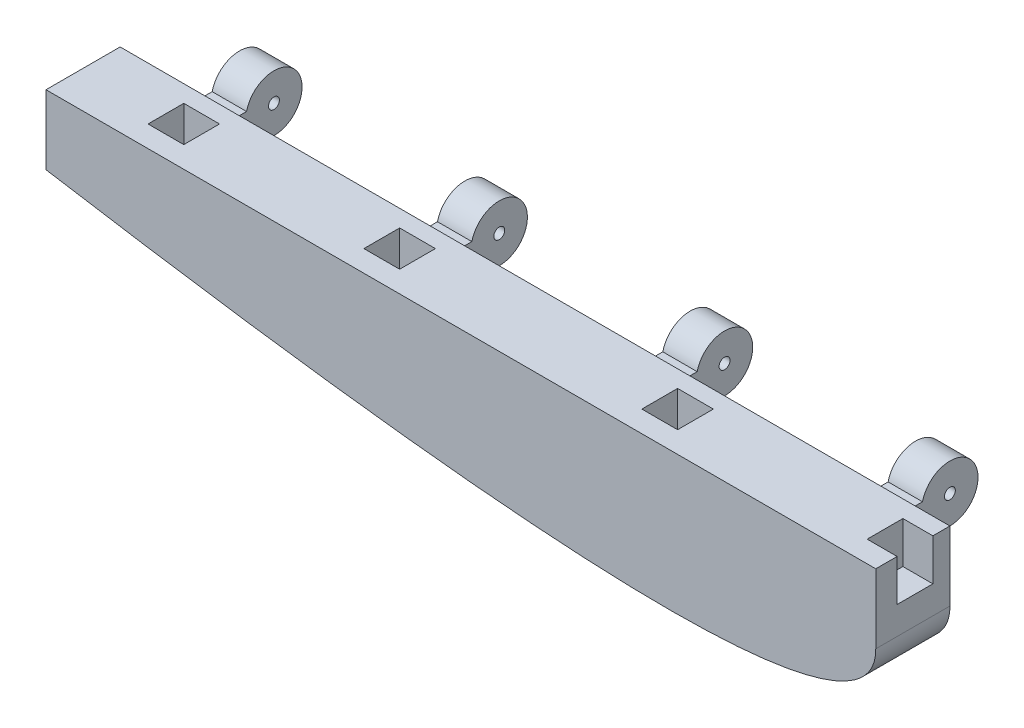
SolidWorks part; units mm, degrees
material "ABS"
ref_plane "Front Plane" through (0, 0, 0) normal (0, 0, 1) x (1, 0, 0)
ref_plane "Top Plane" through (0, 0, 0) normal (0, 1, 0) x (1, 0, 0)
ref_plane "Right Plane" through (0, 0, 0) normal (1, 0, 0) x (0, 0, -1)
sketch "Sketch2" plane through (0, 0, 0) normal (0, 1, 0) x (1, 0, 0)
  line L0 (0, 0) -> (-152, 0)
  line L1 (-152, 0) -> (-152, -152.4)
  line L2 (-152, -152.4) -> (0, -152.4)
  line L3 (0, -152.4) -> (0, 0)
  dimension "D1" = 152.4
  dimension "D2" = 152
extrude "Boss-Extrude2" add sketch "Sketch2" along normal blind 12.7
ref_plane "Plane2" through (-14.9327, 0, 0) normal (1, 0, 0) x (0, 0, -1)
ref_plane "Plane1" through (-12.7, 0, 0) normal (1, 0, 0) x (0, 0, -1)
sketch "Sketch9" plane through (0, 12.7, 0) normal (0, 1, 0) x (1, 0, 0)
  line L0 (0, 0) -> (0, -48.862) construction
  line L1 (0, -152.4) -> (0, 0) construction
  line L2 (-152, 0) -> (-152, -48.862) construction
  line L3 (-152, 0) -> (-152, -152.4) construction
  line L4 (0, 0) -> (-5.4077, 0) construction
  line L5 (0, 0) -> (-152, 0) construction
  dimension "D1" = 48.862
  dimension "D2" = 48.862
  dimension "D3" = 5.4077
ref_axis "Axis2" through (-152, 12.7, 48.862) along (1, 0, 0)
sketch "Sketch3" plane through (-12.7, 0, 0) normal (1, 0, 0) x (0, 0, -1)
  line L0 (0, 6.35) -> (0, 0)
  line L2 (0, 12.7) -> (0, 0) construction
  line L3 (0, 0) -> (12.7, 0)
  line L4 (12.7, 6.1562) -> (12.7, 6.1587)
  line L5 (7.6839, 6.35) -> (0, 6.35)
  arc A3 (12.7, 0) -> (7.6839, 6.35) centre (12.7, 5.1562) ccw
  circle A5 centre (12.7, 5.1562) radius 1
  dimension "D3" = 10.3124
  dimension "D2" = 0
  dimension "D4" = 7.6839
  dimension "D6" = 2
  dimension "D1" = 6.35
  dimension "D5" = 12.7
extrude "Boss-Extrude3" add sketch "Sketch3" against normal blind 6.3 contours A5 L4 L3 A3 | A5 L4 A3 L3 | A3 L5 L0 L3 region at (-12.7, 4.2781, -9.3369)
ref_plane "Plane5" through (0, 0, 24.431) normal (0, 0, -1) x (-1, 0, 0)
ref_plane "Plane6" through (0, 12.7, 0) normal (0, 1, 0) x (1, 0, 0)
sketch "Sketch10" plane through (0, 12.7, 0) normal (0, 1, 0) x (1, 0, 0)
  line L0 (0, 0) -> (-152, 0) construction
  circle A0 centre (-10.2337, -3.175) radius 0.508
  dimension "D1" = 10.2337
  dimension "D3" = 1.016
  dimension "D2" = 3.175
extrude "Cut-Extrude3" [suppressed] cut sketch "Sketch10" against normal blind 9.525
mirror "Mirror1" [suppressed] about plane through (0, 0, 24.431) normal (0, 0, -1)
fillet "Fillet1" radius 1.5875 3 edges at (-19, 3.175, 0) (-15.85, 6.35, 0) (-12.7, 3.175, 0)
pattern_linear "LPattern1" count 4 spacing 41.275 along (-1, 0, 0) of "Boss-Extrude3", "Mirror1", "Fillet1"
sketch "Sketch12" plane through (0, 0, 0) normal (0, 0, -1) x (-1, 0, 0)
  spline S0 degree 1 poles (0, 0) (152, 0) knots 0 0 1 1
  spline S1 degree 2 poles (152, 0) (-0.2287, -25.399) (0, 0) knots 0 0 0 0.553499 0.553499 0.553499
  spline S2 degree 1 poles (0, 0) (152, 0) knots 0 0 1 1
  spline S3 degree 1 poles (152, 0) (0, 0) knots 0 0 1 1
  dimension "D1" = 50.8
extrude "Boss-Extrude4" add sketch "Sketch12" against normal up to surface (152.4 mm away) contours S1 | S0 S1 up to face at (-76, 6.35, 152.4)
sketch "Sketch13" plane through (0, 12.7, 0) normal (0, 1, 0) x (1, 0, 0)
  line L0 (0, -152.4) -> (0, 0) construction
  line L1 (-81.8426, -69.85) -> (-19.05, -69.85)
  line L2 (-81.8426, -69.85) -> (-81.8426, -96.44)
  line L3 (-81.8426, -96.44) -> (-19.05, -96.44)
  line L4 (-19.05, -69.85) -> (-19.05, -96.44)
  line L5 (0, 0) -> (-152, 0) construction
  line L7 (-85.0176, -66.675) -> (-15.875, -66.675)
  line L8 (-85.0176, -66.675) -> (-85.0176, -99.615)
  line L9 (-85.0176, -99.615) -> (-15.875, -99.615)
  line L10 (-15.875, -66.675) -> (-15.875, -99.615)
  dimension "D1" = 62.7926
  dimension "D2" = 26.59
  dimension "D3" = 19.05
  dimension "D4" = 69.85
  dimension "D5" = 3.175
  dimension "D6" = 3.175
  dimension "D7" = 3.175
  dimension "D8" = 3.175
extrude "Boss-Extrude5" add sketch "Sketch13" along normal blind 3.5001
sketch "Sketch14" plane through (0, 12.7, 0) normal (0, 1, 0) x (1, 0, 0)
  line L0 (-19.05, -69.85) -> (-81.8426, -69.85) construction
  line L1 (-81.8426, -69.85) -> (-81.8426, -96.44) construction
  circle A0 centre (-78.1761, -74.1223) radius 1.2497
  circle A1 centre (-22.1767, -74.1223) radius 1.2497
  circle A2 centre (-78.1761, -93.1215) radius 1.2497
  circle A3 centre (-22.1767, -93.1215) radius 1.2497
  dimension "D1" = 4.2723
  dimension "D3" = 3.6665
  dimension "D4" = 55.9994
  dimension "D2" = 18.9992
extrude "Cut-Extrude5" cut sketch "Sketch14" against normal blind 6.35
sketch "Sketch15" plane through (0, 12.7, 0) normal (0, 1, 0) x (1, 0, 0)
  line L0 (-101.2, -152.4) -> (-101.2, -127)
  line L1 (-152, -152.4) -> (0, -152.4) construction
  line L2 (-101.2, -127) -> (-152, -66.4589)
  line L3 (-152, 0) -> (-152, -152.4) construction
  line L4 (-152, -66.4589) -> (-152, -152.4)
  line L5 (-152, -152.4) -> (-101.2, -152.4)
  spline S0 degree 3 poles (-101.2, -127) (-102.2273, -119.2728) (-124.4228, -68.0569) (-152, -66.4589) knots 0 0 0 0 0.841715 0.841715 0.841715 0.841715
  line M9 (-152, 0) -> (-152, -152.4)
  line M10 (-152, -152.4) -> (0, -152.4)
  dimension "D1" = 50.8
  dimension "D2" = 25.4
  dimension "D3" = 220
extrude "Cut-Extrude6" cut sketch "Sketch15" against normal through all contours L2 S0 | L0 L2 M9 M10 region at (-131.2037, 12.7, 121.8215) region at (-125.4187, 12.7, 91.8783)
sketch "Sketch16" plane through (0, 0, 152.4) normal (0, 0, 1) x (1, 0, 0)
  line L0 (-101.2, 12.7) -> (-101.2, 5.3677)
  line L1 (-101.2, 12.7) -> (-117.6978, 3.175)
  line L2 (-101.2, 5.3677) -> (-117.6978, -4.1573)
  line L3 (-117.6978, 3.175) -> (-117.6978, -4.1573)
  line L4 (-101.2, -7.6194) -> (-101.2, 12.7) construction
  dimension "D1" = 6.35
  dimension "D2" = 60
  dimension "D3" = 19.05
extrude "Boss-Extrude6" add sketch "Sketch16" against normal blind 6.35
sketch "Sketch17" plane through (-27.6243, 47.8466, 0) normal (0.5, -0.866, 0) x (0.866, 0.5, 0)
  line L0 (-104.0079, 146.05) -> (-104.0079, 152.4) construction
  circle A0 centre (-104.0079, 149.225) radius 4.826
  dimension "D1" = 9.652
extrude "Boss-Extrude7" add sketch "Sketch17" against normal up to surface (6.35 mm away) up to face at (-109.4489, 7.9375, 149.225)
sketch "Sketch18" plane through (-27.6243, 47.8466, 0) normal (0.5, -0.866, 0) x (0.866, 0.5, 0)
  circle A0 centre (-104.0079, 149.225) radius 1.143
  dimension "D1" = 2.286
extrude "Cut-Extrude8" cut sketch "Sketch18" against normal up to surface (6.35 mm away) up to face at (-113.4243, 5.6423, 149.225)
ref_plane "Plane7" through (-30.7993, 53.3459, 0) normal (-0.5, 0.866, 0) x (0.866, 0.5, 0)
sketch "Sketch20" plane through (-30.7993, 53.3459, 0) normal (-0.5, 0.866, 0) x (0.866, 0.5, 0)
  line L0 (-86.0567, -130.9381) -> (-86.0567, -143.9239)
  line L1 (-86.0567, -143.9239) -> (-62.911, -143.9239)
  line L2 (-62.911, -143.9239) -> (-62.911, -130.9381)
  line L3 (-62.911, -130.9381) -> (-86.0567, -130.9381)
  dimension "D1" = 12.9857
  dimension "D2" = 23.1457
extrude "Cut-Extrude9" cut sketch "Sketch20" against normal blind 15.494
sketch "Sketch21" plane through (-30.7993, 53.3459, 0) normal (-0.5, 0.866, 0) x (0.866, 0.5, 0)
  line L0 (-86.0373, -130.9653) -> (-90.8633, -130.9653)
  line L1 (-90.8633, -130.9653) -> (-90.8633, -143.951)
  line L2 (-90.8633, -143.951) -> (-86.0373, -143.951)
  line L3 (-86.0373, -143.951) -> (-86.0373, -130.9653)
  line L4 (-63.2251, -143.7536) -> (-58.3991, -143.7536)
  line L5 (-58.3991, -143.7536) -> (-58.3991, -130.7678)
  line L6 (-58.3991, -130.7678) -> (-63.2251, -130.7678)
  line L7 (-63.2251, -130.7678) -> (-63.2251, -143.7536)
  line L8 (6.35, -152.4) -> (6.35, 0) construction
  dimension "D1" = 12.9857
  dimension "D2" = 12.9857
  dimension "D3" = 4.826
  dimension "D4" = 22.8122
  dimension "D5" = 4.826
  dimension "D6" = 64.7491
extrude "Boss-Extrude8" add sketch "Sketch21" against normal up to surface (18.046 mm away) up to face at (-89.1246, -1.8694, 79.9709)
sketch "Sketch22" plane through (-30.7993, 53.3459, 0) normal (-0.5, 0.866, 0) x (0.866, 0.5, 0)
  circle A0 centre (-88.4503, -137.587) radius 0.508
  circle A1 centre (-60.8121, -137.587) radius 0.508
  dimension "D1" = 1.016
  dimension "D2" = 1.016
extrude "Cut-Extrude10" cut sketch "Sketch22" against normal blind 10.16
sketch "Esquisse1" plane through (0, 0, 152.4) normal (0, 0, 1) x (1, 0, 0)
  line L0 (-78.1, 4.563) -> (-78.1, 7.7177)
  line L1 (-74.3, 4.1474) -> (-74.3, 7.7177)
  line L2 (-78.1, 4.563) -> (-92.8263, 3.2599)
  line L3 (-92.8263, -0.7245) -> (-78.1, -2.0277)
  line L4 (-78.1, -2.0277) -> (-78.1, -5.1823)
  line L5 (-74.3, -5.1823) -> (-74.3, -1.612)
  line L6 (-73.9909, -1.3823) -> (-62.0409, -0.7293)
  line L7 (-73.9909, 3.9177) -> (-62.0409, 3.2647)
  arc A0 (-78.1, 7.7177) -> (-74.3, 7.7177) centre (-76.2, 7.7177) cw
  arc A2 (-62.0409, 3.2647) -> (-62.0409, -0.7293) centre (-62.15, 1.2677) cw
  arc A3 (-92.8263, 3.2599) -> (-92.8263, -0.7245) centre (-92.65, 1.2677) ccw
  arc A4 (-78.1, -5.1823) -> (-74.3, -5.1823) centre (-76.2, -5.1823) ccw
  arc A5 (-74.3, 4.1474) -> (-73.9909, 3.9177) centre (-76.2, 1.2677) cw
  arc A6 (-73.9909, -1.3823) -> (-74.3, -1.612) centre (-76.2, 1.2677) cw
fillet "Fillet2" radius 6.35 2 edges at (-101.2, 2.5403, 127) (-152, 6.35, 66.4589)
sketch "Sketch23" plane through (-50.5751, -29.1996, 0) normal (0.866, 0.5, 0) x (0, 0, -1)
  line L0 (-139.1816, 51.6925) -> (-139.1816, 50.1685)
  line L1 (-139.1816, 50.1685) -> (-135.6256, 50.1685)
  line L2 (-135.6256, 50.1685) -> (-135.6256, 51.6925)
  line L3 (-135.6256, 51.6925) -> (-139.1816, 51.6925)
  line L4 (-143.7536, 61.5985) -> (-130.7678, 61.5985) construction
  line L5 (-143.7536, 48.3814) -> (-143.7536, 61.5985) construction
  dimension "D1" = 9.906
  dimension "D2" = 4.572
  dimension "D3" = 3.556
  dimension "D4" = 1.524
extrude "Cut-Extrude11" cut sketch "Sketch23" against normal up to surface (4.826 mm away) up to face at (-81.233, 14.2495, 135.1532)
sketch "Esquisse5" plane through (0, 12.7, 0) normal (0, 1, 0) x (1, 0, 0)
  line L0 (-130.7715, -45.6452) -> (-137.1215, -45.6452) construction
  line L1 (-137.1215, -45.6452) -> (-137.1215, -39.2952) construction
  line L2 (-137.1215, -39.2952) -> (-130.7715, -39.2952) construction
  line L3 (-130.7715, -39.2952) -> (-130.7715, -45.6452) construction
  line L4 (-130.7715, -9.5674) -> (-137.1215, -9.5674) construction
  line L5 (-137.1215, -9.5674) -> (-137.1215, -3.2174) construction
  line L6 (-137.1215, -3.2174) -> (-130.7715, -3.2174) construction
  line L7 (-130.7715, -3.2174) -> (-130.7715, -9.5674) construction
  line L8 (-130.7715, -45.6452) -> (-137.1215, -45.6452) construction
  line L9 (-137.1215, -45.6452) -> (-137.1215, -39.2952) construction
  line L10 (-137.1215, -39.2952) -> (-130.7715, -39.2952) construction
  line L11 (-130.7715, -39.2952) -> (-130.7715, -45.6452) construction
  line L12 (-130.7715, -9.5674) -> (-137.1215, -9.5674) construction
  line L13 (-137.1215, -9.5674) -> (-137.1215, -3.2174) construction
  line L14 (-137.1215, -3.2174) -> (-130.7715, -3.2174) construction
  line L15 (-130.7715, -3.2174) -> (-130.7715, -9.5674) construction
  line L16 (-137.2215, -3.1174) -> (-130.6715, -3.1174)
  line L17 (-130.6715, -3.1174) -> (-130.6715, -9.6674)
  line L18 (-130.6715, -9.6674) -> (-137.2215, -9.6674)
  line L19 (-137.2215, -9.6674) -> (-137.2215, -3.1174)
  line L20 (-137.2215, -39.1952) -> (-130.6715, -39.1952)
  line L21 (-130.6715, -39.1952) -> (-130.6715, -45.7452)
  line L22 (-130.6715, -45.7452) -> (-137.2215, -45.7452)
  line L23 (-137.2215, -45.7452) -> (-137.2215, -39.1952)
  dimension "D1" = 0.1
extrude "Enlèv. mat.-Extru.3" cut sketch "Esquisse5" against normal blind 7.62
sketch "Esquisse6" plane through (0, 0, 152.4) normal (0, 0, 1) x (1, 0, 0)
  line L5 (-55.3, -7.62) -> (-46.3, -7.62)
  line L6 (-55.3, -7.62) -> (-55.3, 2.38)
  line L7 (-55.3, 2.38) -> (-46.3, 2.38)
  line L8 (-46.3, -7.62) -> (-46.3, 2.38)
  line L10 (0, 12.7) -> (0, 0) construction
  point P9 (-50.8, 2.38)
  dimension "D1" = 9
  dimension "D2" = 10
  dimension "D3" = 7.62
  dimension "D4" = 50.8
extrude "Boss.-Extru.1" add sketch "Esquisse6" along normal blind 10.922
sketch "Esquisse7" plane through (-55.3, 0, 0) normal (-1, 0, 0) x (0, 0, 1)
  line L1 (163.322, 2.38) -> (163.322, -7.62) construction
  circle A0 centre (163.322, -2.62) radius 5
extrude "Boss.-Extru.2" add sketch "Esquisse7" against normal up to surface (9 mm away) up to face at (-46.3, -2.62, 157.861)
hole_wizard "Dégagement M21" positions "Esquisse8" profile "Esquisse9" hole size "M2" standard "Ansi Metric" end condition up to next
sketch "Esquisse8" plane through (-55.3, 0, 0) normal (-1, 0, 0) x (0, 0, 1)
  line L1 (152.4, 2.38) -> (152.4, -7.62) construction
  point P0 (163.322, -2.62)
  point P15 (152.4, -2.62)
sketch "Esquisse9" plane through (-55.3, -2.62, 163.322) normal (0, 1, 0) x (0, 0, 1)
  line L0 (0, 0) -> (0, 9)
  line L1 (0, 9) -> (3.5, 9)
  line L2 (3.5, 9) -> (3.5, 0)
  line L5 (3.5, 0) -> (0, 0)
  line L11 (0, -6.35) -> (0, 107.95) construction
  dimension "Diamètre du perçage jusqu'au prochain" = 7
  dimension "Profondeur du perçage jusqu'au prochain" = 9
pattern_linear "Répétition linéaire1" count 3 spacing 20 along (1, 0, 0) count 3 spacing 20 along (-1, 0, 0) of "Boss.-Extru.1", "Dégagement M21", "Boss.-Extru.2" pattern seed only yes
sketch "Esquisse10" plane through (0, 12.7, 0) normal (0, -1, 0) x (1, 0, 0)
  line L1 (-53.34, 142.4581) -> (-63.34, 142.4581)
  line L2 (-53.34, 142.4581) -> (-53.34, 132.4581)
  line L3 (-53.34, 132.4581) -> (-63.34, 132.4581)
  line L4 (-63.34, 142.4581) -> (-63.34, 132.4581)
  line L5 (-55.3, 152.4) -> (-46.3, 152.4) construction
  line L6 (-101.2, 143.951) -> (-101.2, 130.9653) construction
  point P4 (-63.34, 137.4581)
  point P8 (-50.8, 152.4)
  point P10 (-101.2, 137.4581)
  dimension "D1" = 10
  dimension "D2" = 10
  dimension "D3" = 2.54
extrude "Boss.-Extru.3" add sketch "Esquisse10" against normal blind 10
sketch "Esquisse11" plane through (-53.34, 0, 0) normal (1, 0, 0) x (0, 0, -1)
  line L0 (-132.4581, 22.7) -> (-142.4581, 22.7) construction
  circle A0 centre (-138.1731, 22.7) radius 5.715
  dimension "D1" = 11.43
extrude "Boss.-Extru.4" add sketch "Esquisse11" against normal up to surface (10 mm away) up to face at (-63.34, 17.7, 137.4581)
sketch "Esquisse13" plane through (-53.34, 0, 0) normal (1, 0, 0) x (0, 0, -1)
  circle A0 centre (-138.1731, 22.7) radius 1.3
  arc A2 (-132.4581, 22.7) -> (-142.4581, 18.9185) centre (-138.1731, 22.7) ccw construction
  dimension "D1" = 2.6
extrude "Enlèv. mat.-Extru.4" cut sketch "Esquisse13" against normal up to next
sketch "Esquisse14" plane through (0, 12.7, 0) normal (0, 1, 0) x (1, 0, 0)
  line L0 (-91.2294, -39.2952) -> (-91.2294, -45.6452) construction
  line L1 (-91.2294, -45.6452) -> (-97.5794, -45.6452) construction
  line L2 (-97.5794, -45.6452) -> (-97.5794, -39.2952) construction
  line L3 (-97.5794, -39.2952) -> (-91.2294, -39.2952) construction
  line L4 (-46.6615, -45.6452) -> (-46.6615, -39.2952) construction
  line L5 (-40.3115, -45.6452) -> (-46.6615, -45.6452) construction
  line L6 (-40.3115, -39.2952) -> (-40.3115, -45.6452) construction
  line L7 (-46.6615, -39.2952) -> (-40.3115, -39.2952) construction
  line L8 (-5.3865, -45.6455) -> (-5.3865, -39.2955) construction
  line L9 (-5.3865, -39.2955) -> (0.9635, -39.2955) construction
  line L10 (0.9635, -39.2955) -> (0.9635, -45.6455) construction
  line L11 (0.9635, -45.6455) -> (-5.3865, -45.6455) construction
  line L12 (0.9635, -9.5677) -> (-5.3865, -9.5677) construction
  line L13 (-5.3865, -9.5677) -> (-5.3865, -3.2177) construction
  line L14 (-5.3865, -3.2177) -> (0.9635, -3.2177) construction
  line L15 (0.9635, -3.2177) -> (0.9635, -9.5677) construction
  line L16 (-40.3115, -3.2174) -> (-40.3115, -9.5674) construction
  line L17 (-46.6615, -3.2174) -> (-40.3115, -3.2174) construction
  line L18 (-46.6615, -9.5674) -> (-46.6615, -3.2174) construction
  line L19 (-40.3115, -9.5674) -> (-46.6615, -9.5674) construction
  line L20 (-91.2294, -9.5674) -> (-97.5794, -9.5674) construction
  line L21 (-91.2294, -3.2174) -> (-91.2294, -9.5674) construction
  line L22 (-97.5794, -3.2174) -> (-91.2294, -3.2174) construction
  line L23 (-97.5794, -9.5674) -> (-97.5794, -3.2174) construction
  line L24 (-91.2294, -39.2952) -> (-91.2294, -45.6452) construction
  line L25 (-91.2294, -45.6452) -> (-97.5794, -45.6452) construction
  line L26 (-97.5794, -45.6452) -> (-97.5794, -39.2952) construction
  line L27 (-97.5794, -39.2952) -> (-91.2294, -39.2952) construction
  line L28 (-46.6615, -45.6452) -> (-46.6615, -39.2952) construction
  line L29 (-40.3115, -45.6452) -> (-46.6615, -45.6452) construction
  line L30 (-40.3115, -39.2952) -> (-40.3115, -45.6452) construction
  line L31 (-46.6615, -39.2952) -> (-40.3115, -39.2952) construction
  line L32 (-5.3865, -45.6455) -> (-5.3865, -39.2955) construction
  line L33 (-5.3865, -39.2955) -> (0.9635, -39.2955) construction
  line L34 (0.9635, -39.2955) -> (0.9635, -45.6455) construction
  line L35 (0.9635, -45.6455) -> (-5.3865, -45.6455) construction
  line L36 (0.9635, -9.5677) -> (-5.3865, -9.5677) construction
  line L37 (-5.3865, -9.5677) -> (-5.3865, -3.2177) construction
  line L38 (-5.3865, -3.2177) -> (0.9635, -3.2177) construction
  line L39 (0.9635, -3.2177) -> (0.9635, -9.5677) construction
  line L40 (-40.3115, -3.2174) -> (-40.3115, -9.5674) construction
  line L41 (-46.6615, -3.2174) -> (-40.3115, -3.2174) construction
  line L42 (-46.6615, -9.5674) -> (-46.6615, -3.2174) construction
  line L43 (-40.3115, -9.5674) -> (-46.6615, -9.5674) construction
  line L44 (-91.2294, -9.5674) -> (-97.5794, -9.5674) construction
  line L45 (-91.2294, -3.2174) -> (-91.2294, -9.5674) construction
  line L46 (-97.5794, -3.2174) -> (-91.2294, -3.2174) construction
  line L47 (-97.5794, -9.5674) -> (-97.5794, -3.2174) construction
  line L48 (-91.1294, -39.1952) -> (-91.1294, -45.7452)
  line L49 (-91.1294, -45.7452) -> (-97.6794, -45.7452)
  line L50 (-97.6794, -45.7452) -> (-97.6794, -39.1952)
  line L51 (-97.6794, -39.1952) -> (-91.1294, -39.1952)
  line L52 (-46.7615, -45.7452) -> (-46.7615, -39.1952)
  line L53 (-46.7615, -39.1952) -> (-40.2115, -39.1952)
  line L54 (-40.2115, -39.1952) -> (-40.2115, -45.7452)
  line L55 (-40.2115, -45.7452) -> (-46.7615, -45.7452)
  line L56 (-5.4865, -45.7455) -> (-5.4865, -39.1955)
  line L57 (-5.4865, -39.1955) -> (1.0635, -39.1955)
  line L58 (1.0635, -39.1955) -> (1.0635, -45.7455)
  line L59 (1.0635, -45.7455) -> (-5.4865, -45.7455)
  line L60 (1.0635, -9.6677) -> (-5.4865, -9.6677)
  line L61 (-5.4865, -9.6677) -> (-5.4865, -3.1177)
  line L62 (-5.4865, -3.1177) -> (1.0635, -3.1177)
  line L63 (1.0635, -3.1177) -> (1.0635, -9.6677)
  line L64 (-40.2115, -3.1174) -> (-40.2115, -9.6674)
  line L65 (-40.2115, -9.6674) -> (-46.7615, -9.6674)
  line L66 (-46.7615, -9.6674) -> (-46.7615, -3.1174)
  line L67 (-46.7615, -3.1174) -> (-40.2115, -3.1174)
  line L68 (-91.1294, -9.6674) -> (-97.6794, -9.6674)
  line L69 (-97.6794, -9.6674) -> (-97.6794, -3.1174)
  line L70 (-97.6794, -3.1174) -> (-91.1294, -3.1174)
  line L71 (-91.1294, -3.1174) -> (-91.1294, -9.6674)
  dimension "D1" = 0.1
extrude "Enlèv. mat.-Extru.5" cut sketch "Esquisse14" against normal blind 7.62
sketch "Esquisse15" plane through (0, 12.7, 0) normal (0, 1, 0) x (1, 0, 0)
  line L1 (-166.3767, -13.5798) -> (47.4441, -13.5798)
  line L2 (-166.3767, -13.5798) -> (-166.3767, -179.935)
  line L3 (-166.3767, -179.935) -> (47.4441, -179.935)
  line L4 (47.4441, -13.5798) -> (47.4441, -179.935)
extrude "Enlèv. mat.-Extru.6" cut sketch "Esquisse15" against normal through all and the other way through all
